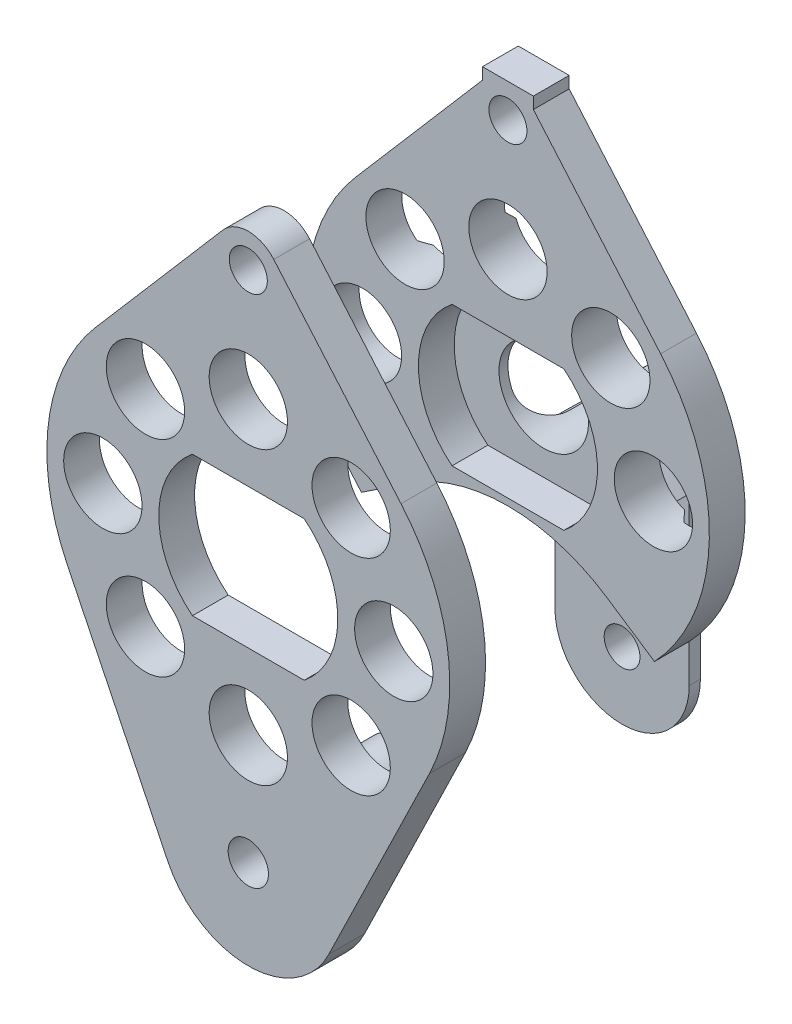
SolidWorks part; units mm, degrees
ref_plane "Front Plane" through (0, 0, 0) normal (0, 0, 1) x (1, 0, 0)
ref_plane "Top Plane" through (0, 0, 0) normal (0, 1, 0) x (1, 0, 0)
ref_plane "Right Plane" through (0, 0, 0) normal (1, 0, 0) x (0, 0, -1)
sketch "Sketch1" plane through (0, 0, 0) normal (0, 0, 1) x (1, 0, 0)
  line L0 (-13.6452, 11.7391) -> (-2.2742, 24.9565)
  line L1 (2.2742, 24.9565) -> (13.6452, 11.7391)
  line L2 (-4.9054, -6) -> (4.9054, -6)
  line L3 (4.9054, 6) -> (-4.9054, 6)
  line L4 (-4.9054, -6) -> (4.9054, -6)
  line L5 (4.9054, 6) -> (-4.9054, 6)
  arc A0 (-13.6452, 11.7391) -> (13.6452, 11.7391) centre (0, 0) ccw
  arc A1 (-2.2742, 24.9565) -> (2.2742, 24.9565) centre (0, 23) cw
  arc A2 (-4.9054, 6) -> (-4.9054, -6) centre (0, 0) ccw
  arc A3 (4.9054, -6) -> (4.9054, 6) centre (0, 0) ccw
  arc A4 (-4.9054, 6) -> (-4.9054, -6) centre (0, 0) ccw
  arc A5 (4.9054, -6) -> (4.9054, 6) centre (0, 0) ccw
  circle A6 centre (0, 23) radius 1.7
  dimension "D2" = 36
  dimension "D3" = 3.4
  dimension "D5" = 3
  dimension "D4" = 23
  dimension "D1" = 0
extrude "Boss-Extrude1" add sketch "Sketch1" against normal blind 3.2
sketch "Sketch2" plane through (0, 0, -3.2) normal (0, 0, -1) x (-1, 0, 0)
  line L2 (13.6452, 11.7391) -> (2.2742, 24.9565)
  line L3 (-2.2742, 24.9565) -> (-13.6452, 11.7391)
  line L4 (13.6452, 11.7391) -> (2.2742, 24.9565)
  line L5 (-2.2742, 24.9565) -> (-13.6452, 11.7391)
  line L6 (4.9054, 6) -> (-4.9054, 6)
  line L7 (-4.9054, -6) -> (4.9054, -6)
  line L8 (4.9054, 6) -> (-4.9054, 6)
  line L9 (-4.9054, -6) -> (4.9054, -6)
  arc A0 (7.5749, -16.3285) -> (-7.5749, -16.3285) centre (0, -22.857) ccw
  arc A1 (7.5749, -16.3285) -> (13.6452, 11.7391) centre (0, 0) ccw
  arc A2 (-13.6452, 11.7391) -> (13.6452, 11.7391) centre (0, 0) ccw
  arc A3 (2.2742, 24.9565) -> (-2.2742, 24.9565) centre (0, 23) ccw
  arc A4 (-13.6452, 11.7391) -> (-7.5749, -16.3285) centre (0, 0) ccw
  arc A5 (2.2742, 24.9565) -> (-2.2742, 24.9565) centre (0, 23) ccw
  arc A6 (4.9054, -6) -> (4.9054, 6) centre (0, 0) ccw
  arc A7 (-4.9054, 6) -> (-4.9054, -6) centre (0, 0) ccw
  arc A8 (4.9054, -6) -> (4.9054, 6) centre (0, 0) ccw
  arc A9 (-4.9054, 6) -> (-4.9054, -6) centre (0, 0) ccw
  circle A10 centre (0, 23) radius 1.7
  dimension "D3" = 20
  dimension "D1" = 0
  dimension "D2" = 0
extrude "Boss-Extrude2" add sketch "Sketch2" along normal blind 3.2 from offset 20 separate body
sketch "Sketch4" plane through (0, 0, 0) normal (0, 0, 1) x (1, 0, 0)
  line L0 (7.1937, -26.3571) -> (16.1859, -7.875)
  line L1 (16.1859, -7.875) -> (-16.1859, -7.875)
  line L2 (-16.1859, -7.875) -> (-7.1937, -26.3571)
  circle A0 centre (0, -22.857) radius 1.8
  circle A1 centre (0, -22.857) radius 8
  arc A2 (-13.6452, 11.7391) -> (13.6452, 11.7391) centre (0, 0) ccw construction
  arc M8 (-13.6452, 11.7391) -> (13.6452, 11.7391) centre (0, 0) ccw
  dimension "D1" = 3.6
  dimension "D2" = 16
extrude "Boss-Extrude3" add sketch "Sketch4" against normal up to surface (3.2 mm away) contours A1 L0 M8 | A1 A0 M8 | A1 L2 M8 region at (9.7731, -17.5045, 0) region at (0, -30.6461, 0) region at (-9.7731, -17.5045, 0) up to face at (1.7, 23, -3.2)
sketch "Sketch5" plane through (0, 0, -26.4) normal (0, 0, -1) x (-1, 0, 0)
  line L0 (-1.5, -3.7081) -> (-6, -8.0247)
  line L1 (1.5, -3.7081) -> (6, -8.0247)
  circle A7 centre (0, -22.857) radius 16
  circle A8 centre (0, 0) radius 4
  line M3 (4.9054, -6) -> (-4.9054, -6)
  dimension "D1" = 32
  dimension "D2" = 12
  dimension "D3" = 8
  dimension "D4" = 3
extrude "Boss-Extrude4" add sketch "Sketch5" along normal blind 7 contours A8 L0 L1 M3 | A7 L1 L0 M3 region at (0, -5.0833, -26.4) region at (0, -6.6659, -26.4)
sketch "Sketch6" plane through (0, 0, -26.4) normal (0, 0, -1) x (-1, 0, 0)
  arc A0 (6, -8.0247) -> (-6, -8.0247) centre (0, 0) ccw
  circle A1 centre (0, 0) radius 4
  arc A3 (6, -8.0247) -> (-6, -8.0247) centre (0, -22.857) ccw
extrude "Boss-Extrude5" add sketch "Sketch6" along normal blind 0.8
sketch "Sketch7" plane through (0, 0, -33.4) normal (0, 0, -1) x (-1, 0, 0)
  line L0 (1.5, -3.7081) -> (6, -8.0247)
  line L1 (6, -8.0247) -> (6, -22.857)
  line L2 (-6, -22.857) -> (-6, -8.0247)
  line L3 (-6, -8.0247) -> (-1.5, -3.7081)
  line L4 (1.5, -3.7081) -> (6, -8.0247) construction
  line L5 (-1.5, -3.7081) -> (-6, -8.0247) construction
  arc A0 (6, -22.857) -> (-6, -22.857) centre (0, -22.857) cw
  arc A1 (-1.5, -3.7081) -> (1.5, -3.7081) centre (0, 0) ccw
  arc A3 (-1.5, -3.7081) -> (1.5, -3.7081) centre (0, 0) ccw construction
  point P2 (0, 0)
  point P10 (0, 0)
  point P11 (0, 0)
  point P13 (1.5, -3.7081)
  point P16 (0, 0)
  point P23 (-1.5, -3.7081)
  point P25 (-1.5, -3.7081)
  point P26 (0, -3.1748)
  point P27 (0, -3.1748)
  point P29 (0, 0)
  point P30 (-6, -8.0247)
  point P33 (6, -8.0247)
extrude "Boss-Extrude6" add sketch "Sketch7" along normal blind 4
sketch "Sketch8" plane through (0, 0, -37.4) normal (0, 0, -1) x (-1, 0, 0)
  circle A0 centre (0, -22.857) radius 1.6
  dimension "D1" = 3.2
extrude "Cut-Extrude1" cut sketch "Sketch8" against normal through all
sketch "Sketch9" plane through (0, 0, -3.2) normal (0, 0, -1) x (-1, 0, 0)
  circle A0 centre (0, -22.857) radius 1.8
  circle A1 centre (0, -22.857) radius 3
  dimension "D1" = 6
extrude "Boss-Extrude7" add sketch "Sketch9" along normal offset from surface (10.2 mm away) 20 up to face at (-1.6, -22.857, -33.4)
fillet "Fillet1" radius 3 2 edges at (3.75, -5.8664, -27.2) (-3.75, -5.8664, -27.2)
chamfer "Chamfer1" distance 3 angle 45 1 edges at (0, 10.0197, -26.4)
sketch "Sketch11" plane through (0, 0, -26.4) normal (0, 0, -1) x (-1, 0, 0)
  line L0 (-8.8638, -9.5366) -> (-13.0937, -12.3513)
  line L1 (-13.0937, -12.3513) -> (-10.9484, -20.2744)
  line L2 (-10.9484, -20.2744) -> (19.2962, -16.4787)
  line L3 (19.2962, -16.4787) -> (8.8638, -9.5366)
  arc A0 (8.8638, -9.5366) -> (-8.8638, -9.5366) centre (0, -22.857) ccw construction
  arc A1 (8.8638, -9.5366) -> (-8.8638, -9.5366) centre (0, -22.857) ccw
  arc A2 (-13.6452, 11.7391) -> (-7.5749, -16.3285) centre (0, 0) ccw construction
extrude "Cut-Extrude3" cut sketch "Sketch11" against normal blind 10
sketch "Sketch12" plane through (0, 0, -3.2) normal (0, 0, -1) x (-1, 0, 0)
  circle A0 centre (13, 0) radius 3.5
  circle A1 centre (9.1924, -9.1924) radius 3.5
  circle A2 centre (0, -13) radius 3.5
  circle A3 centre (-9.1924, -9.1924) radius 3.5
  circle A4 centre (-13, 0) radius 3.5
  circle A5 centre (-9.1924, 9.1924) radius 3.5
  circle A6 centre (0, 13) radius 3.5
  circle A7 centre (9.1924, 9.1924) radius 3.5
  point P19 (0, 0)
  dimension "D1" = 13
  dimension "D2" = 7
  dimension "D3" = 8
extrude "Cut-Extrude4" cut sketch "Sketch12" against normal blind 16
extrude "Cut-Extrude5" cut sketch "Sketch12<2>" along normal blind 50 contours A0 | A7 | A6 | A5 | A4 region at (-13, 0, -3.2) region at (13, 0, -3.2) region at (9.1924, 9.1924, -3.2) region at (0, 13, -3.2) region at (-9.1924, 9.1924, -3.2)
sketch "Sketch12<2>" plane through (0, 0, -3.2) normal (0, 0, -1) x (-1, 0, 0) same geometry as "Sketch12"
chamfer "Chamfer2" distance 3 angle 45 3 edges at (6, -15.4408, -37.4) (-6, -15.4408, -37.4) (0, -28.857, -37.4)
sketch "Sketch16" plane through (0, 0, -26.4) normal (0, 0, -1) x (-1, 0, 0)
  line L0 (-2.2742, 24.9565) -> (-2.2742, 26)
  line L1 (-2.2742, 26) -> (2.2742, 26)
  line L2 (2.2742, 26) -> (2.2742, 24.9565)
  line L3 (-2.2742, 24.9565) -> (2.2742, 24.9565)
  arc A0 (2.2742, 24.9565) -> (-2.2742, 24.9565) centre (0, 23) ccw construction
extrude "Boss-Extrude8" add sketch "Sketch16" against normal up to surface (3.2 mm away) up to face at (-12.6924, 9.1924, -23.2)
sketch "Sketch17" plane through (0, 0, 0) normal (0, 0, 1) x (1, 0, 0)
  line L6 (-4.9937, -6.25) -> (4.9937, -6.25)
  line L7 (4.9937, 6.25) -> (-4.9937, 6.25)
  line L8 (-4.9937, -6.25) -> (4.9937, -6.25)
  line L9 (4.9937, 6.25) -> (-4.9937, 6.25)
  arc A8 (4.9937, -6.25) -> (4.9937, 6.25) centre (0, 0) ccw
  arc A9 (-4.9937, 6.25) -> (-4.9937, -6.25) centre (0, 0) ccw
  arc A10 (4.9937, -6.25) -> (4.9937, 6.25) centre (0, 0) ccw
  arc A11 (-4.9937, 6.25) -> (-4.9937, -6.25) centre (0, 0) ccw
  dimension "D1" = 0.25
extrude "Cut-Extrude6" cut sketch "Sketch17" against normal up to surface (26.4 mm away) up to face at (0, 0, -26.4)
